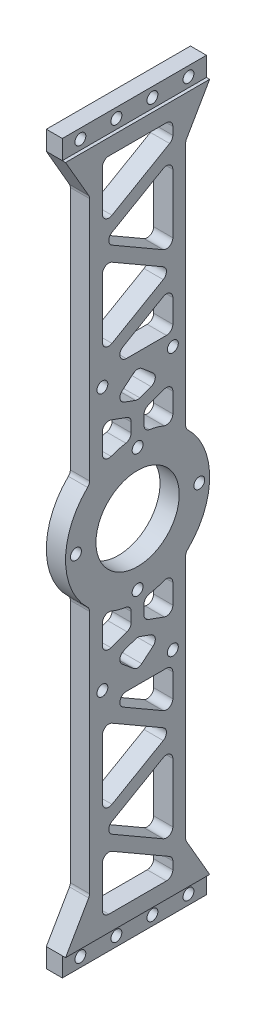
SolidWorks part; units mm, degrees
material "Сплав 2024"
ref_plane "Спереди" through (0, 0, 0) normal (0, 0, 1) x (1, 0, 0)
ref_plane "Сверху" through (0, 0, 0) normal (0, 1, 0) x (1, 0, 0)
ref_plane "Справа" through (0, 0, 0) normal (1, 0, 0) x (0, 0, -1)
sketch "Эскиз1" plane through (0, 0, 0) normal (0, 1, 0) x (1, 0, 0)
  line L1 (0, 0) -> (6, 0)
  line L2 (0, 0) -> (0, -30)
  line L3 (0, -30) -> (6, -30)
  line L4 (6, 0) -> (6, -30)
  dimension "D1" = 6
  dimension "D2" = 30
extrude "Бобышка-Вытянуть1" add sketch "Эскиз1" along normal blind 227
sketch "Эскиз2" plane through (0, 0, 0) normal (-1, 0, 0) x (0, 0, 1)
  line L0 (30, 113.5) -> (0, 113.5) construction
  line L1 (30, 227) -> (30, 0) construction
  line L2 (0, 227) -> (0, 0) construction
  line L3 (15, 227) -> (15, 0) construction
  line L4 (0, 227) -> (30, 227) construction
  line L5 (0, 0) -> (30, 0) construction
  circle A0 centre (15, 113.5) radius 22.5
  dimension "D1" = 45
extrude "Бобышка-Вытянуть2" add sketch "Эскиз2" against normal up to surface (6 mm away) up to face at (6, 113.5, 15)
sketch "Эскиз3" plane through (0, 0, 0) normal (-1, 0, 0) x (0, 0, 1)
  circle A0 centre (15, 113.5) radius 13
  dimension "D1" = 26
extrude "Вырез-Вытянуть1" cut sketch "Эскиз3" against normal through all
sketch "Эскиз4" plane through (6, 0, 0) normal (-1, 0, 0) x (0, 0, 1)
  line L0 (15, 136) -> (15, 91) construction
  line L1 (15, 227) -> (15, 0) construction
  line L2 (37.5, 113.5) -> (-7.5, 113.5) construction
  circle A0 centre (15, 113.5) radius 19.25 construction
  circle A1 centre (15, 113.5) radius 22.5 construction
  dimension "D1" = 38.5
hole_wizard "Отверстие с зазором M32" positions "Эскиз6" profile "Эскиз5" hole size "M3" standard "Ansi Metric" end condition up to next
sketch "Эскиз6" plane through (6, -25.0247, 7.2629) normal (-1, 0, 0) x (0, 0, 1)
  line L0 (7.7371, 161.0247) -> (7.7371, 116.0247) construction
  line L1 (30.2371, 138.5247) -> (-14.7629, 138.5247) construction
  circle A0 centre (7.7371, 138.5247) radius 19.25 construction
  point P0 (7.7371, 157.7747)
  point P6 (-11.5129, 138.5247)
  point P10 (7.7371, 119.2747)
  point P12 (26.9871, 138.5247)
sketch "Эскиз5" plane through (6, 132.75, 15) normal (0, 1, 0) x (0, 0, -1)
  line L0 (0, 0) -> (0, 6)
  line L1 (0, 6) -> (1.7, 6)
  line L2 (1.7, 6) -> (1.7, 0)
  line L5 (1.7, 0) -> (0, 0)
  line L11 (0, -6.35) -> (0, 107.95) construction
  dimension "Диаметр сквозного отверстия" = 3.4
  dimension "Глубина сквозного отверстия" = 6
sketch "Эскиз8" plane through (6, 0, 0) normal (1, 0, 0) x (0, 0, -1)
  line L0 (-15, 227) -> (-15, 0) construction
  line L1 (-30, 227) -> (0, 227) construction
  line L2 (-30, 0) -> (0, 0) construction
  line L3 (19.447, 113.5) -> (-49.447, 113.5) construction
  line L4 (0, 227) -> (0, 130.2705) construction
  line L5 (-26, 154.5) -> (-4, 154.5) construction
  line L6 (-26, 154.5) -> (-26, 72.5) construction
  line L7 (-26, 72.5) -> (-4, 72.5) construction
  line L8 (-4, 154.5) -> (-4, 72.5) construction
  line L9 (-30, 227) -> (-30, 130.2705) construction
  line L11 (-26, 154.5) -> (-4, 72.5) construction
  line L12 (-4, 154.5) -> (-26, 72.5) construction
  point P8 (-15, 113.5)
  point P9 (-15, 113.5)
  dimension "D1" = 4
  dimension "D2" = 82
  dimension "D4" = 4
hole_wizard "Отверстие с зазором M33" positions "Эскиз10" profile "Эскиз9" hole size "M3" standard "Ansi Metric" end condition through all
sketch "Эскиз10" plane through (6, 0, 0) normal (1, 0, 0) x (0, 0, -1)
  point P0 (-26, 154.5)
  point P3 (-4, 154.5)
  point P6 (-4, 72.5)
  point P9 (-26, 72.5)
sketch "Эскиз9" plane through (6, 154.5, 26) normal (0, 1, 0) x (0, 0, -1)
  line L0 (0, 0) -> (0, 6)
  line L1 (0, 6) -> (1.7, 6)
  line L2 (1.7, 6) -> (1.7, 0)
  line L5 (1.7, 0) -> (0, 0)
  line L11 (0, -6.35) -> (0, 107.95) construction
  dimension "Диаметр сквозного отверстия" = 3.4
  dimension "Глубина сквозного отверстия" = 6
sketch "Эскиз11" plane through (6, 0, 0) normal (1, 0, 0) x (0, 0, -1)
  line L0 (-15, 227) -> (-15, 0) construction
  line L1 (-30, 227) -> (0, 227) construction
  line L2 (-30, 0) -> (0, 0) construction
  line L3 (-37.5, 221) -> (-30, 208.0096)
  line L4 (-37.5, 221) -> (7.5, 221) construction
  line L5 (-37.5, 221) -> (-37.5, 227)
  line L6 (-37.5, 227) -> (7.5, 227)
  line L7 (7.5, 221) -> (7.5, 227)
  line L8 (-37.5, 221) -> (7.5, 227) construction
  line L9 (-37.5, 227) -> (7.5, 221) construction
  line L10 (-30, 227) -> (-30, 130.2705) construction
  line L11 (-30, 208.0096) -> (0, 208.0096)
  line L12 (0, 227) -> (0, 130.2705) construction
  line L13 (0, 208.0096) -> (7.5, 221)
  line L14 (-37.5, 224) -> (7.5, 224) construction
  line L15 (-31.875, 227) -> (-31.875, 221) construction
  line L16 (-26.25, 227) -> (-26.25, 221) construction
  line L17 (-20.625, 227) -> (-20.625, 221) construction
  line L18 (-15, 227) -> (-15, 221) construction
  line L19 (-15, 113.5) -> (-3.75, 113.5) construction
  line L20 (-15, 0) -> (-15, 6) construction
  line L21 (-20.625, 0) -> (-20.625, 6) construction
  line L22 (-26.25, 0) -> (-26.25, 6) construction
  line L23 (-31.875, 0) -> (-31.875, 6) construction
  line L24 (-37.5, 3) -> (7.5, 3) construction
  line L25 (-37.5, 0) -> (7.5, 6) construction
  line L26 (-37.5, 6) -> (7.5, 0) construction
  line L27 (-37.5, 6) -> (7.5, 6) construction
  line L28 (0, 18.9904) -> (7.5, 6)
  line L29 (-30, 18.9904) -> (0, 18.9904)
  line L30 (7.5, 6) -> (7.5, 0)
  line L31 (-37.5, 0) -> (7.5, 0)
  line L32 (-37.5, 6) -> (-37.5, 0)
  line L33 (-37.5, 6) -> (-30, 18.9904)
  line L34 (-9.375, 227) -> (-9.375, 221) construction
  line L35 (-3.75, 221) -> (-3.75, 227) construction
  line L36 (1.875, 227) -> (1.875, 221) construction
  line L37 (-9.375, 0) -> (-9.375, 6) construction
  line L38 (-3.75, 6) -> (-3.75, 0) construction
  line L39 (1.875, 0) -> (1.875, 6) construction
  point P6 (-15, 224)
  point P45 (-15, 3)
  dimension "D1" = 6
  dimension "D2" = 45
  dimension "D3" = 120
  dimension "D4" = 5.625
  dimension "D5" = 5.625
  dimension "D6" = 5.625
  dimension "D7" = 5.625
  dimension "D8" = 5.625
  dimension "D9" = 5.625
  dimension "D10" = 5.625
extrude "Бобышка-Вытянуть3" add sketch "Эскиз11" against normal up to surface (6 mm away) up to face at (0, 154.5, 24.3)
hole_wizard "Отверстие с зазором M31" positions "Эскиз13" profile "Эскиз12" hole size "M3" standard "Ansi Metric" end condition through all
sketch "Эскиз13" plane through (6, 0, 0) normal (1, 0, 0) x (0, 0, -1)
  line L0 (-31.875, 227) -> (-31.875, 221) construction
  line L4 (-31.875, 0) -> (-31.875, 6) construction
  line L8 (1.875, 227) -> (1.875, 221) construction
  line L9 (-9.375, 227) -> (-9.375, 221) construction
  line L10 (-20.625, 227) -> (-20.625, 221) construction
  line L11 (1.875, 0) -> (1.875, 6) construction
  line L12 (-9.375, 0) -> (-9.375, 6) construction
  line L13 (-20.625, 0) -> (-20.625, 6) construction
  point P0 (-31.875, 224)
  point P4 (-20.625, 224)
  point P8 (-9.375, 224)
  point P12 (1.875, 224)
  point P16 (-31.875, 3)
  point P20 (-20.625, 3)
  point P24 (-9.375, 3)
  point P28 (1.875, 3)
sketch "Эскиз12" plane through (6, 224, 31.875) normal (0, 1, 0) x (0, 0, -1)
  line L0 (0, 0) -> (0, 6)
  line L1 (0, 6) -> (1.7, 6)
  line L2 (1.7, 6) -> (1.7, 0)
  line L5 (1.7, 0) -> (0, 0)
  line L11 (0, -6.35) -> (0, 107.95) construction
  dimension "Диаметр сквозного отверстия" = 3.4
  dimension "Глубина сквозного отверстия" = 6
sketch "Эскиз14" plane through (6, 0, 0) normal (1, 0, 0) x (0, 0, -1)
  line L1 (-37.5, 227) -> (7.5, 227)
  line L2 (-37.5, 227) -> (-37.5, 221)
  line L3 (-37.5, 221) -> (7.5, 221)
  line L4 (7.5, 227) -> (7.5, 221)
  line L5 (-37.5, 0) -> (7.5, 0)
  line L6 (-37.5, 0) -> (-37.5, 6)
  line L7 (-37.5, 6) -> (7.5, 6)
  line L8 (7.5, 0) -> (7.5, 6)
extrude "Вырез-Вытянуть2" cut sketch "Эскиз14" against normal blind 1
sketch "Эскиз15" plane through (0, 0, 0) normal (-1, 0, 0) x (0, 0, 1)
  line L0 (4, 0) -> (4, 227) construction
  line L1 (-7.5, 0) -> (37.5, 0) construction
  line L2 (-7.5, 227) -> (37.5, 227) construction
  line L3 (26, 227) -> (26, 0) construction
  line L4 (0, 96.7295) -> (0, 18.9904) construction
  line L5 (30, 96.7295) -> (30, 18.9904) construction
  line L6 (13, 91.0891) -> (13, 85.0058)
  line L7 (17, 91.0891) -> (17, 85.0058)
  line L8 (15, 227) -> (15, 0) construction
  line L9 (17, 85.0058) -> (26, 81.7301)
  line L10 (13, 85.0058) -> (4, 81.7301)
  line L11 (7.5382, 78.7612) -> (15, 81.4771)
  line L12 (15, 81.4771) -> (22.4618, 78.7612)
  line L13 (22.4618, 78.7612) -> (15, 72.5)
  line L14 (15, 72.5) -> (7.5382, 78.7612)
  line L15 (0, 78.7612) -> (30, 78.7612) construction
  line L16 (4, 81.7301) -> (4, 93.8722)
  line L17 (26, 81.7301) -> (26, 93.8722)
  line L18 (4, 72.5) -> (26, 72.5) construction
  line L19 (4, 81.7301) -> (15, 72.5) construction
  line L20 (26, 81.7301) -> (15, 72.5) construction
  line L21 (-7.5, 6) -> (37.5, 6) construction
  line L22 (-4.6132, 11) -> (34.6132, 11) construction
  line L23 (0, 18.9904) -> (-7.5, 6) construction
  line L24 (37.5, 6) -> (30, 18.9904) construction
  line L25 (4, 68.5) -> (26, 68.5)
  line L26 (26, 68.5) -> (4, 55.7983)
  line L27 (4, 55.7983) -> (4, 68.5)
  line L28 (4, 51.1795) -> (26, 63.8812)
  line L29 (26, 63.8812) -> (26, 38.4778)
  line L30 (26, 38.4778) -> (4, 51.1795)
  line L31 (4, 46.5607) -> (26, 33.859)
  line L32 (26, 33.859) -> (4, 21.1573)
  line L33 (4, 21.1573) -> (4, 46.5607)
  line L34 (4, 11) -> (4, 16.5385)
  line L35 (26, 29.2402) -> (26, 11)
  line L36 (26, 11) -> (4, 11)
  line L37 (4, 16.5385) -> (26, 29.2402)
  line L38 (15, 113.5) -> (28, 113.5) construction
  line L39 (4, 171.2017) -> (4, 158.5)
  line L40 (26, 145.2699) -> (26, 133.1278)
  line L41 (4, 145.2699) -> (4, 133.1278)
  line L42 (13, 141.9942) -> (4, 145.2699)
  line L43 (13, 135.9109) -> (13, 141.9942)
  line L44 (17, 135.9109) -> (17, 141.9942)
  line L45 (17, 141.9942) -> (26, 145.2699)
  line L46 (15, 145.5229) -> (22.4618, 148.2388)
  line L47 (7.5382, 148.2388) -> (15, 145.5229)
  line L48 (15, 154.5) -> (7.5382, 148.2388)
  line L49 (22.4618, 148.2388) -> (15, 154.5)
  line L50 (4, 158.5) -> (26, 158.5)
  line L51 (26, 158.5) -> (4, 171.2017)
  line L52 (4, 175.8205) -> (26, 163.1188)
  line L53 (26, 163.1188) -> (26, 188.5222)
  line L54 (26, 188.5222) -> (4, 175.8205)
  line L55 (4, 180.4393) -> (26, 193.141)
  line L56 (4, 205.8427) -> (4, 180.4393)
  line L57 (26, 193.141) -> (4, 205.8427)
  line L58 (4, 216) -> (4, 210.4615)
  line L59 (4, 210.4615) -> (26, 197.7598)
  line L60 (26, 197.7598) -> (26, 216)
  line L61 (26, 216) -> (4, 216)
  circle A0 centre (15, 113.5) radius 22.5 construction
  arc A1 (4, 93.8722) -> (13, 91.0891) centre (15, 113.5) ccw
  circle A2 centre (15, 113.5) radius 13 construction
  arc A3 (17, 91.0891) -> (26, 93.8722) centre (15, 113.5) ccw
  arc A4 (17, 135.9109) -> (26, 133.1278) centre (15, 113.5) cw
  arc A5 (4, 133.1278) -> (13, 135.9109) centre (15, 113.5) cw
  point P12 (4, 93.8722)
  point P13 (26, 93.8722)
  dimension "D3" = 4
  dimension "D1" = 4
  dimension "D2" = 4
  dimension "D4" = 2
  dimension "D5" = 110
  dimension "D6" = 4
  dimension "D7" = 100
  dimension "D8" = 5
  dimension "D9" = 30
  dimension "D10" = 60
  dimension "D11" = 60
  dimension "D12" = 4
  dimension "D13" = 4
  dimension "D14" = 4
  dimension "D15" = 4
extrude "Вырез-Вытянуть3" cut sketch "Эскиз15" against normal up to next
fillet "Скругление1" radius 2 58 edges at (3, 171.2017, 4) (3, 11, 26) (3, 29.2402, 26) (3, 11, 4) (3, 16.5385, 4) (3, 21.1573, 4) (3, 46.5607, 4) (3, 33.859, 26) (3, 38.4778, 26) (3, 63.8812, 26) (3, 51.1795, 4) (3, 55.7983, 4) (3, 68.5, 26) (3, 68.5, 4) (3, 85.0058, 17) (3, 93.8722, 26) (3, 78.7612, 22.4618) (3, 91.0891, 13) (3, 72.5, 15) (3, 81.7301, 26) (3, 85.0058, 13) (3, 81.4771, 15) (3, 91.0891, 17) (3, 78.7612, 7.5382) (3, 81.7301, 4) (3, 93.8722, 4) (3, 148.2388, 7.5382) (3, 148.2388, 22.4618) (3, 141.9942, 13) (3, 145.2699, 26) (3, 133.1278, 26) (3, 135.9109, 13) (3, 145.5229, 15) (3, 135.9109, 17) (3, 133.1278, 4) (3, 141.9942, 17) (3, 154.5, 15) (3, 145.2699, 4) (3, 188.5222, 26) (3, 175.8205, 4) (3, 163.1188, 26) (3, 158.5, 26) (3, 193.141, 26) (3, 158.5, 4) (3, 180.4393, 4) (3, 205.8427, 4) (3, 216, 26) (3, 197.7598, 26) (3, 210.4615, 4) (3, 216, 4) (3, 208.0096, 30) (3, 208.0096, 0) (3, 130.2705, 0) (3, 96.7295, 0) (3, 96.7295, 30) (3, 130.2705, 30) (3, 18.9904, 30) (3, 18.9904, 0)
equation "\"D4@Эскиз11\"=\"D2@Эскиз11\"/8"
equation "\"D5@Эскиз11\"=\"D4@Эскиз11\""
equation "\"D6@Эскиз11\"=\"D4@Эскиз11\""
equation "\"D7@Эскиз11\"=\"D4@Эскиз11\""
equation "\"D8@Эскиз11\"=\"D4@Эскиз11\""
equation "\"D9@Эскиз11\"=\"D4@Эскиз11\""
equation "\"D10@Эскиз11\"=\"D4@Эскиз11\""
